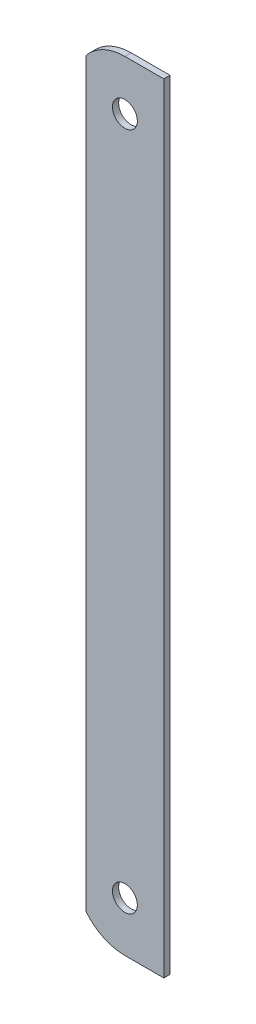
SolidWorks part; units mm, degrees
ref_plane "Front Plane" through (0, 0, 0) normal (0, 0, 1) x (1, 0, 0)
ref_plane "Top Plane" through (0, 0, 0) normal (0, 1, 0) x (1, 0, 0)
ref_plane "Right Plane" through (0, 0, 0) normal (1, 0, 0) x (0, 0, -1)
sketch "Sketch1" plane through (0, 0, 0) normal (0, 0, 1) x (1, 0, 0)
  line L0 (-12.5, 0) -> (12.5, 0) construction
  line L1 (3.5, 125) -> (12.5, 125)
  line L2 (-12.5, 109) -> (-12.5, -109)
  line L3 (3.5, -125) -> (12.5, -125)
  line L4 (12.5, 125) -> (12.5, -125)
  line L5 (-12.5, 125) -> (12.5, -125) construction
  line L6 (-12.5, -125) -> (12.5, 125) construction
  line L7 (-12.5, 109) -> (-12.5, 125) construction
  line L8 (-12.5, 125) -> (3.5, 125) construction
  line L9 (-12.5, 109) -> (-12.5, 125) construction
  line L10 (-12.5, 109) -> (-12.5, 118.9875)
  line L11 (3.5, 125) -> (0, 125)
  line L12 (-12.5, -109) -> (-12.5, -118.9875)
  line L13 (3.5, -125) -> (0, -125)
  circle A0 centre (0, 109) radius 4
  circle A1 centre (0, -109) radius 4
  arc A4 (0, 125) -> (-12.5, 118.9875) centre (0, 109) ccw
  arc A6 (-12.5, -118.9875) -> (0, -125) centre (0, -109) ccw
  point P0 (0, 0)
  dimension "D4" = 8
  dimension "D7" = 32
  dimension "D1" = 25
  dimension "D3" = 218
  dimension "D6" = 250
extrude "Boss-Extrude1" add sketch "Sketch1" along normal blind 2
